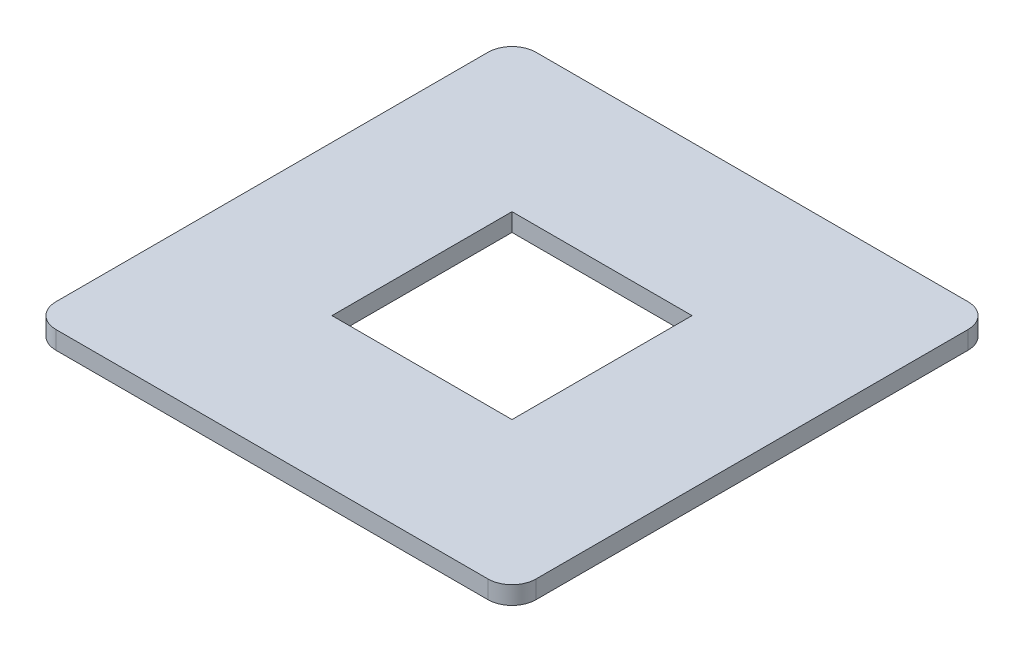
SolidWorks part; units mm, degrees
ref_plane "Front Plane" through (0, 0, 0) normal (0, 0, 1) x (1, 0, 0)
ref_plane "Top Plane" through (0, 0, 0) normal (0, 1, 0) x (1, 0, 0)
ref_plane "Right Plane" through (0, 0, 0) normal (1, 0, 0) x (0, 0, -1)
sketch "Sketch2" plane through (0, 0, 0) normal (0, 1, 0) x (1, 0, 0)
  line L1 (-100, -100) -> (100, -100)
  line L2 (-100, -100) -> (-100, 100)
  line L3 (-100, 100) -> (100, 100)
  line L4 (100, -100) -> (100, 100)
  line L5 (-100, -100) -> (100, 100) construction
  line L6 (-100, 100) -> (100, -100) construction
  point P0 (0, 0)
  dimension "D1" = 200
  dimension "D2" = 200
extrude "Base" add sketch "Sketch2" along normal blind 7.5
sketch "Sketch3" plane through (0, 7.5, 0) normal (0, 1, 0) x (1, 0, 0)
  line L1 (-37.5, -37.5) -> (37.5, -37.5)
  line L2 (-37.5, -37.5) -> (-37.5, 37.5)
  line L3 (-37.5, 37.5) -> (37.5, 37.5)
  line L4 (37.5, -37.5) -> (37.5, 37.5)
  line L5 (-37.5, -37.5) -> (37.5, 37.5) construction
  line L6 (-37.5, 37.5) -> (37.5, -37.5) construction
  point P0 (0, 0)
  dimension "D1" = 75
  dimension "D2" = 75
extrude "Hole" cut sketch "Sketch3" against normal up to surface (7.5 mm away) up to face at (0, 0, 0)
fillet "Fillet1" radius 10 4 edges at (-100, 3.75, -100) (-100, 3.75, 100) (100, 3.75, -100) (100, 3.75, 100)
